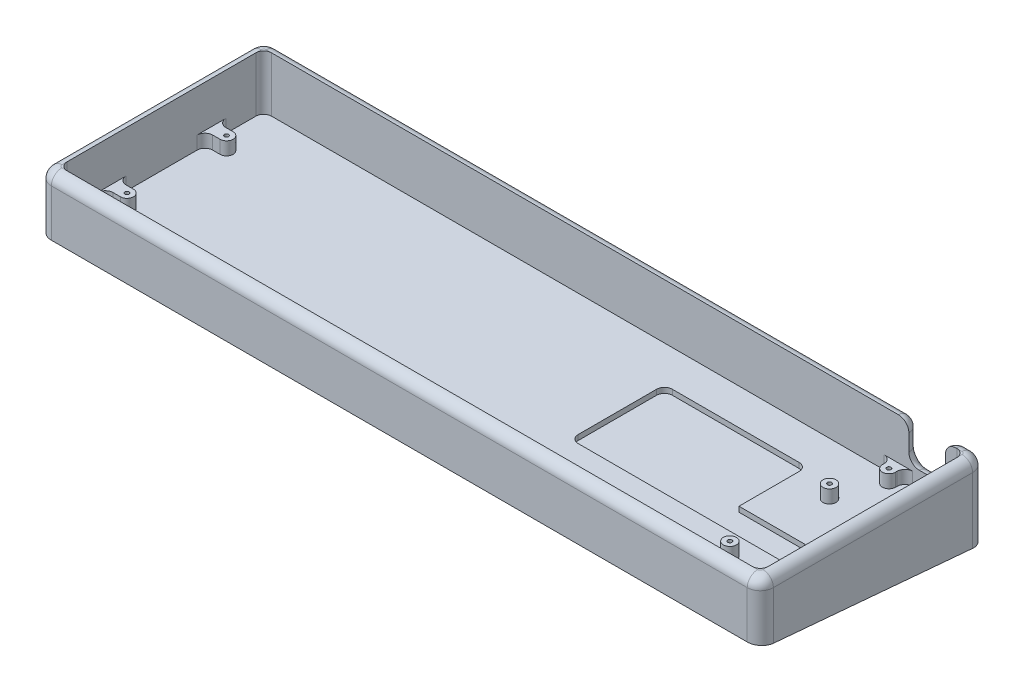
SolidWorks part; units mm, degrees
ref_plane "Front Plane" through (0, 0, 0) normal (0, 0, 1) x (1, 0, 0)
ref_plane "Top Plane" through (0, 0, 0) normal (0, 1, 0) x (1, 0, 0)
ref_plane "Right Plane" through (0, 0, 0) normal (1, 0, 0) x (0, 0, -1)
sketch "Sketch1" plane through (0, 0, 0) normal (1, 0, 0) x (0, 0, -1)
  line L0 (43.1, -11) -> (43.1, -18.54)
  line L1 (43.1, -11) -> (-43.1, -11) construction
  line L2 (43.1, -11) -> (43.1, 11)
  line L3 (43.1, 11) -> (-43.1, 11)
  line L4 (-43.1, -11) -> (-43.1, 11)
  line L5 (43.1, -11) -> (-43.1, 11) construction
  line L6 (43.1, 11) -> (-43.1, -11) construction
  line L7 (43.1, -18.54) -> (-43.1, -11)
  point P0 (0, 0)
  dimension "D1" = 86.2
  dimension "D2" = 22
  dimension "D3" = 7.54
extrude "Boss-Extrude1" add sketch "Sketch1" along normal blind 276.125
sketch "Sketch3" plane through (0, 11, 0) normal (0, 1, 0) x (1, 0, 0)
  line L0 (276.125, -43.1) -> (0, -43.1) construction
  line L1 (276.125, 43.1) -> (276.125, -43.1) construction
  line L2 (276.125, 43.1) -> (0, 43.1) construction
  line L3 (0, 43.1) -> (0, -43.1) construction
  line L4 (276.125, -43.1) -> (0, -43.1) construction
  line L5 (276.125, 43.1) -> (276.125, -43.1) construction
  line L6 (276.125, 43.1) -> (0, 43.1) construction
  line L7 (0, 43.1) -> (0, -43.1) construction
  line L8 (272.125, -39.1) -> (4, -39.1)
  line L9 (4, 39.1) -> (4, -39.1)
  line L10 (272.125, 39.1) -> (4, 39.1)
  line L11 (272.125, 39.1) -> (272.125, -39.1)
  dimension "D1" = 4
extrude "Cut-Extrude1" cut sketch "Sketch3" against normal blind 21
sketch "Sketch4" plane through (0, 0, -39.1) normal (0, 0, 1) x (1, 0, 0)
  line L0 (272.125, 11) -> (4, 11) construction
  line L1 (264.755, 11) -> (250.755, 11)
  line L2 (264.755, 11) -> (264.755, -3.4)
  line L3 (264.755, -3.4) -> (250.755, -3.4)
  line L4 (250.755, 11) -> (250.755, -3.4)
  line L5 (272.125, -10) -> (272.125, 11) construction
  dimension "D1" = 7.37
  dimension "D2" = 14.4
  dimension "D3" = 14
extrude "Cut-Extrude2" cut sketch "Sketch4" against normal blind 4
fillet "Fillet1" radius 5 4 edges at (0, 0, 43.1) (0, -3.77, -43.1) (276.125, -3.77, -43.1) (276.125, 0, 43.1)
fillet "Fillet4" radius 3 4 edges at (4, 0.5, -39.1) (4, 0.5, 39.1) (272.125, 0.5, 39.1) (272.125, 0.5, -39.1)
fillet "Fillet5" radius 4 4 edges at (264.755, -3.4, -41.1) (264.755, 11, -41.1) (250.755, -3.4, -41.1) (250.755, 11, -41.1)
fillet "Fillet6" radius 4 16 edges at (274.6605, 11, 41.6355) (276.125, 11, 0) (274.6605, 11, -41.6355) (269.94, 11, -43.1) (265.9266, 9.8284, -43.1) (264.755, 3.8, -43.1) (263.5834, -2.2284, -43.1) (257.755, -3.4, -43.1) (251.9266, -2.2284, -43.1) (250.755, 3.8, -43.1) (249.5834, 9.8284, -43.1) (125.8775, 11, -43.1) (1.4645, 11, -41.6355) (0, 11, 0) (1.4645, 11, 41.6355) (138.0625, 11, 43.1)
sketch "Sketch5" plane through (0, -10, 0) normal (0, 1, 0) x (1, 0, 0)
  line L0 (269.125, 39.1) -> (7, 39.1) construction
  line L1 (272.125, -36.1) -> (272.125, 36.1) construction
  line L2 (9.8, 21.6) -> (4, 21.6)
  line L3 (4, 36.1) -> (4, -36.1) construction
  line L4 (9.8, 16.6) -> (4, 16.6)
  line L5 (4, 16.6) -> (4, 21.6)
  line L6 (9.8, -16.5) -> (4, -16.5)
  line L7 (4, -16.5) -> (4, -21.5)
  line L8 (4, -21.5) -> (9.8, -21.5)
  line L9 (244.225, 35.5) -> (244.225, 39.1)
  line L10 (244.225, 39.1) -> (249.225, 39.1)
  line L11 (249.225, 39.1) -> (249.225, 35.5)
  line L12 (265.995, 35.5) -> (265.995, 39.1)
  line L13 (268.495, 33) -> (272.125, 33)
  line L14 (272.125, 33) -> (272.125, 36.1)
  line L15 (265.995, 39.1) -> (269.125, 39.1)
  line L16 (249.225, -35.5) -> (249.225, -39.1)
  line L17 (268.495, -33) -> (272.125, -33)
  line L18 (272.125, -33) -> (272.125, -36.1)
  line L19 (249.225, -39.1) -> (244.225, -39.1)
  line L20 (7, -39.1) -> (269.125, -39.1) construction
  line L21 (244.225, -39.1) -> (244.225, -35.5)
  line L22 (265.995, -35.5) -> (265.995, -39.1)
  line L23 (265.995, -39.1) -> (269.125, -39.1)
  arc A0 (9.8, 16.6) -> (9.8, 21.6) centre (9.8, 19.1) ccw
  circle A1 centre (240.4, 19.1) radius 2.5
  circle A2 centre (240.4, -19) radius 2.5
  arc A3 (268.495, -33) -> (265.995, -35.5) centre (268.495, -35.5) ccw
  arc A4 (265.995, 35.5) -> (268.495, 33) centre (268.495, 35.5) ccw
  arc A5 (244.225, 35.5) -> (249.225, 35.5) centre (246.725, 35.5) ccw
  arc A6 (249.225, -35.5) -> (244.225, -35.5) centre (246.725, -35.5) ccw
  arc A7 (9.8, -21.5) -> (9.8, -16.5) centre (9.8, -19) ccw
  arc A8 (272.125, 36.1) -> (269.125, 39.1) centre (269.125, 36.1) ccw construction
  arc A9 (272.125, 36.1) -> (269.125, 39.1) centre (269.125, 36.1) ccw
  arc A10 (269.125, -39.1) -> (272.125, -36.1) centre (269.125, -36.1) ccw construction
  arc A11 (269.125, -39.1) -> (272.125, -36.1) centre (269.125, -36.1) ccw
  dimension "D2" = 5
  dimension "D3" = 5
  dimension "D8" = 5
  dimension "D9" = 5
  dimension "D12" = 5
  dimension "D15" = 5
  dimension "D20" = 5
  dimension "D22" = 5
  dimension "D1" = 20
  dimension "D4" = 20
  dimension "D5" = 31.725
  dimension "D6" = 31.725
  dimension "D7" = 58.1
  dimension "D10" = 3.63
  dimension "D11" = 74.6
  dimension "D13" = 3.6
  dimension "D14" = 3.63
  dimension "D16" = 3.6
  dimension "D17" = 25.4
  dimension "D18" = 74.6
  dimension "D19" = 25.4
  dimension "D21" = 262.325
  dimension "D23" = 58.1
  dimension "D24" = 262.325
extrude "Boss-Extrude2" add sketch "Sketch5" along normal blind 5
fillet "Fillet7" radius 3 12 edges at (272.125, -7.5, 33) (265.995, -7.5, 39.1) (249.225, -7.5, 39.1) (244.225, -7.5, 39.1) (272.125, -7.5, -33) (265.995, -7.5, -39.1) (249.225, -7.5, -39.1) (244.225, -7.5, -39.1) (4, -7.5, 21.5) (4, -7.5, 16.5) (4, -7.5, -16.6) (4, -7.5, -21.6)
ref_plane "Plane2" through (0, -5, 0) normal (0, 1, 0) x (1, 0, 0)
sketch "Sketch6" plane through (0, -5, 0) normal (0, 1, 0) x (1, 0, 0)
  point P0 (9.8, 19.1)
  point P1 (9.8, -19)
  point P3 (240.4, -19)
  point P5 (240.4, 19.1)
  point P7 (246.725, 35.5)
  point P9 (268.495, 35.5)
  point P11 (268.495, -35.5)
  point P13 (246.725, -35.5)
hole_wizard "M2x0.4 Tapped Hole4" positions "Sketch8" profile "Sketch7" tap size "M2x0.4" standard "ANSI Metric"
sketch "Sketch8" plane through (0, -5, 0) normal (0, 1, 0) x (1, 0, 0)
  point P1 (9.8, 19.1)
  point P4 (9.8, -19)
  point P7 (240.4, 19.1)
  point P10 (240.4, -19)
  point P13 (246.725, 35.5)
  point P16 (268.495, 35.5)
  point P19 (268.495, -35.5)
  point P22 (246.725, -35.5)
  point P28 (0, 0)
sketch "Sketch7" plane through (9.8, -5, -19.1) normal (1, 0, 0) x (0, 0, 1)
  line L0 (0, 0) -> (0, 4.2)
  line L1 (0, 4.2) -> (0.8, 3.7193)
  line L2 (0.8, 3.7193) -> (0.8, 0)
  line L5 (0.8, 0) -> (0, 0)
  line L10 (0, 4.2) -> (-0.8, 3.7193) construction
  line L11 (0, -6.35) -> (0, 107.95) construction
  dimension "Tap Drill Dia." = 1.6
  dimension "Tap Drill Depth" = 4.2
  dimension "Drill Angle" = 118
cosmetic thread "Hole Thread1" parameters "D1"=3, "D2"=2
cosmetic thread "Hole Thread2" parameters "D1"=3, "D2"=2
cosmetic thread "Hole Thread3" parameters "D1"=3, "D2"=2
cosmetic thread "Hole Thread4" parameters "D1"=3, "D2"=2
cosmetic thread "Hole Thread5" parameters "D1"=3, "D2"=2
cosmetic thread "Hole Thread6" parameters "D1"=3, "D2"=2
cosmetic thread "Hole Thread7" parameters "D1"=3, "D2"=2
cosmetic thread "Hole Thread8" parameters "D1"=3, "D2"=2
sketch "Sketch9" plane through (0, -10, 0) normal (0, 1, 0) x (1, 0, 0)
  line L0 (262.995, 39.1) -> (252.225, 39.1) construction
  line L1 (243.575, -10.7) -> (253.575, -10.7)
  line L3 (243.575, -0.7) -> (253.575, -0.7)
  line L4 (253.575, -10.7) -> (253.575, -0.7)
  line L7 (243.575, -0.7) -> (225.575, -0.7)
  line L8 (225.575, -0.7) -> (225.575, 25.3)
  line L9 (225.575, 25.3) -> (171.075, 25.3)
  line L10 (171.075, 25.3) -> (171.075, -10.7)
  line L11 (171.075, -10.7) -> (243.575, -10.7)
  point P0 (248.575, -5.7)
  dimension "D1" = 44.8
  dimension "D2" = 10
  dimension "D3" = 10
  dimension "D4" = 18
  dimension "D5" = 36
  dimension "D6" = 54.5
extrude "Cut-Extrude3" cut sketch "Sketch9" against normal blind 2
fillet "Fillet8" radius 3 5 edges at (253.575, -11, 10.7) (171.075, -11, 10.7) (253.575, -11, 0.7) (225.575, -11, -25.3) (171.075, -11, -25.3)
sketch "Sketch10" plane through (0, -14.6579, 1.2821) normal (0, -0.9962, 0.0871) x (1, 0, 0)
  line L0 (276.125, 36.9584) -> (276.125, -39.5325) construction
  line L1 (271.125, -44.5516) -> (5, -44.5516) construction
  line L2 (271.125, 41.9775) -> (5, 41.9775) construction
  line L3 (0, 36.9584) -> (0, -39.5325) construction
  circle A0 centre (266.125, -34.5516) radius 5
  circle A1 centre (266.125, 31.9775) radius 5
  circle A2 centre (10, 31.9775) radius 5
  circle A3 centre (10, -34.5516) radius 5
  dimension "D1" = 10
  dimension "D2" = 10
  dimension "D3" = 10
  dimension "D4" = 10
  dimension "D5" = 10
  dimension "D6" = 10
  dimension "D7" = 10
  dimension "D8" = 10
  dimension "D9" = 10
  dimension "D10" = 10
  dimension "D11" = 10
  dimension "D12" = 10
extrude "Cut-Extrude4" cut sketch "Sketch10" against normal blind 0.5
